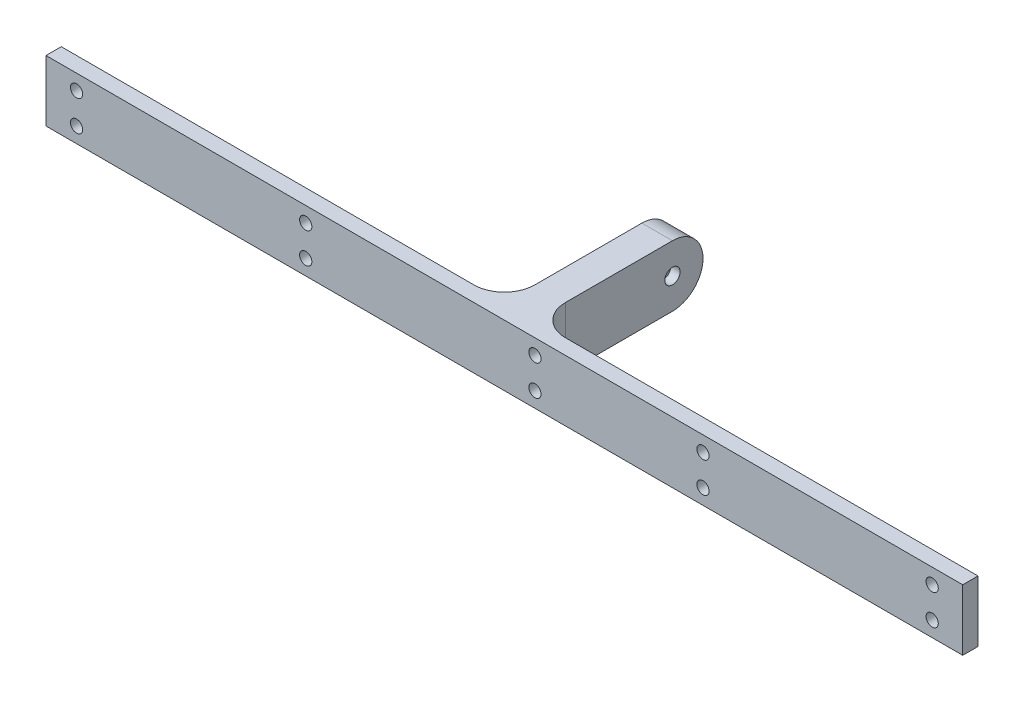
SolidWorks part; units mm, degrees
ref_plane "Plan de face" through (0, 0, 0) normal (0, 0, 1) x (1, 0, 0)
ref_plane "Plan de dessus" through (0, 0, 0) normal (0, 1, 0) x (1, 0, 0)
ref_plane "Plan de droite" through (0, 0, 0) normal (1, 0, 0) x (0, 0, -1)
sketch "Esquisse1" plane through (0, 0, 0) normal (0, 0, 1) x (1, 0, 0)
  line L1 (-150, 10) -> (150, 10)
  line L2 (-150, 10) -> (-150, -10)
  line L3 (-150, -10) -> (150, -10)
  line L4 (150, 10) -> (150, -10)
  dimension "D1" = 150
  dimension "D2" = 300
  dimension "D3" = 20
  dimension "D4" = 10
extrude "Boss.-Extru.1" add sketch "Esquisse1" along normal blind 5
sketch "Esquisse2" plane through (0, 0, 5) normal (0, 0, 1) x (1, 0, 0)
  line L0 (-150, 10) -> (-150, -10) construction
  line L1 (-150, -10) -> (150, -10) construction
  line L2 (150, 10) -> (-150, 10) construction
  line L3 (150, 10) -> (-150, 10) construction
  line L4 (150, -10) -> (150, 10) construction
  circle A0 centre (-140, 5) radius 2
  circle A1 centre (-140, -5) radius 2
  circle A2 centre (-65, 5) radius 2
  circle A3 centre (-65, -5) radius 2
  circle A4 centre (10, 5) radius 2
  circle A5 centre (10, -5) radius 2
  circle A6 centre (65, 5) radius 2
  circle A7 centre (65, -5) radius 2
  circle A8 centre (140, 5) radius 2
  circle A9 centre (140, -5) radius 2
  dimension "D1" = 4
  dimension "D2" = 4
  dimension "D3" = 4
  dimension "D4" = 4
  dimension "D5" = 4
  dimension "D6" = 4
  dimension "D7" = 4
  dimension "D8" = 4
  dimension "D9" = 4
  dimension "D10" = 4
  dimension "D16" = 5
  dimension "D17" = 5
  dimension "D18" = 5
  dimension "D19" = 5
  dimension "D20" = 5
  dimension "D21" = 5
  dimension "D22" = 5
  dimension "D23" = 10
  dimension "D24" = 10
  dimension "D25" = 85
  dimension "D26" = 85
  dimension "D27" = 140
  dimension "D28" = 140
  dimension "D29" = 85
  dimension "D30" = 85
  dimension "D11" = 10
  dimension "D12" = 10
  dimension "D13" = 5
  dimension "D14" = 5
  dimension "D15" = 5
extrude "Enlèv. mat.-Extru.1" cut sketch "Esquisse2" against normal blind 5
sketch "Esquisse3" plane through (0, 0, 0) normal (0, 0, -1) x (-1, 0, 0)
  line L0 (150, -10) -> (-150, -10) construction
  line L1 (-5, -10) -> (5, -10)
  line L2 (-5, -10) -> (-5, 10)
  line L3 (-5, 10) -> (5, 10)
  line L4 (5, -10) -> (5, 10)
  line L5 (-150, 10) -> (150, 10) construction
  dimension "D1" = 5
  dimension "D2" = 5
extrude "Boss.-Extru.2" add sketch "Esquisse3" along normal blind 55
fillet "Congé1" radius 10 2 edges at (-5, 0, 0) (5, 0, 0)
fillet "Congé2" radius 10 2 edges at (0, -10, -55) (0, 10, -55)
sketch "Esquisse4" plane through (-5, 0, 0) normal (-1, 0, 0) x (0, 0, 1)
  line L0 (-45, 10) -> (-10, 10) construction
  circle A0 centre (-45, 0) radius 1.5
  dimension "D1" = 3
  dimension "D2" = 10
  dimension "D3" = 10
extrude "Enlèv. mat.-Extru.2" cut sketch "Esquisse4" against normal blind 35
sketch "Esquisse6" plane through (5, 0, 0) normal (1, 0, 0) x (0, 0, -1)
  circle A0 centre (45, 0) radius 2.5
  dimension "D1" = 5
extrude "Enlèv. mat.-Extru.3" cut sketch "Esquisse6" against normal blind 3
